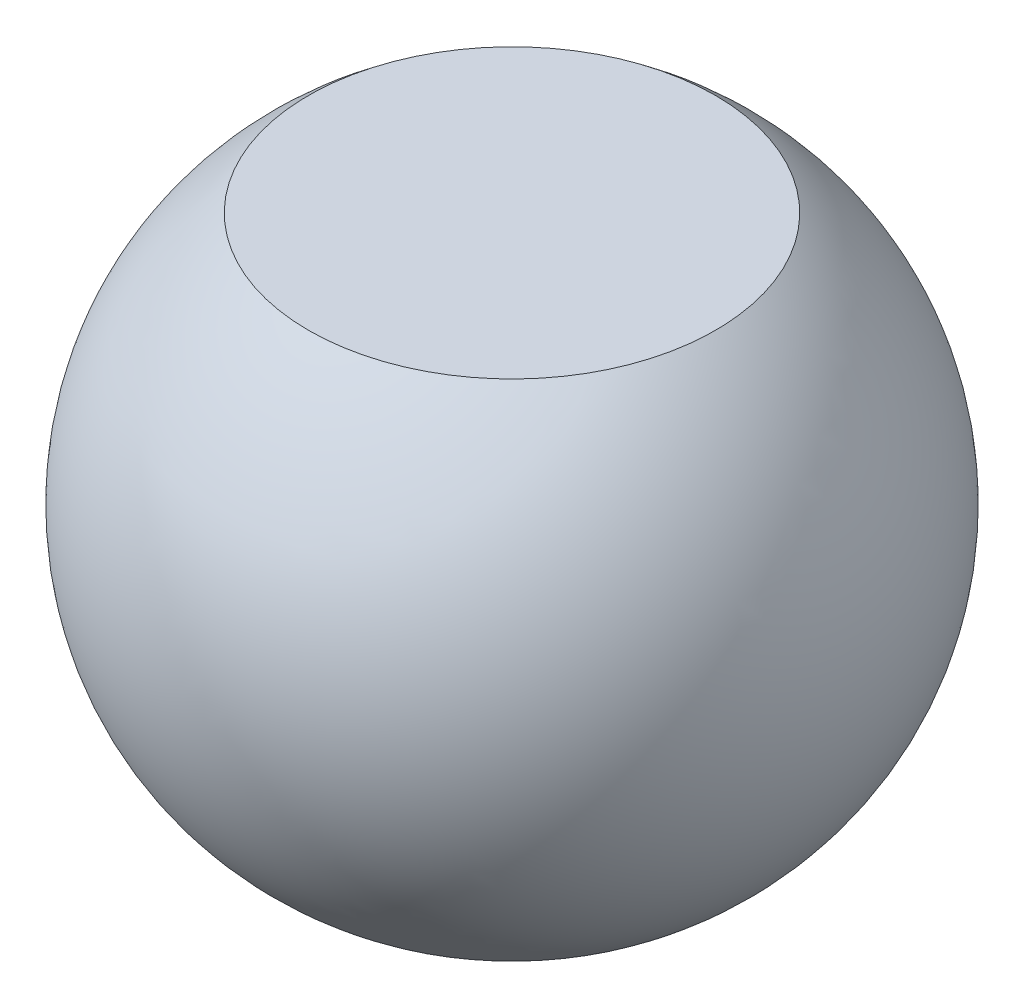
SolidWorks part; units mm, degrees
ref_plane "Front Plane" through (0, 0, 0) normal (0, 0, 1) x (1, 0, 0)
ref_plane "Top Plane" through (0, 0, 0) normal (0, 1, 0) x (1, 0, 0)
ref_plane "Right Plane" through (0, 0, 0) normal (1, 0, 0) x (0, 0, -1)
sketch "Sketch2" plane through (0, 0, 0) normal (1, 0, 0) x (0, 0, -1)
  line L0 (0, 0) -> (0, 805) construction
  line L1 (0, 0) -> (323, 0) construction
  line L2 (323, 0) -> (0, 0)
  line L3 (0, 805) -> (324.4168, 805)
  line L4 (0, 0) -> (0, 805)
  arc A0 (323, 0) -> (324.4168, 805) centre (23.7135, 403.028) ccw
  dimension "D3" = 502
  dimension "D1" = 323
  dimension "D2" = 805
revolve "Revolve1" add sketch "Sketch2" angle 360 about L4
sketch "Sketch3" plane through (0, 0, 0) normal (0, 0, 1) x (1, 0, 0)
  line L0 (-893, 784) -> (-745.515, 820.7721)
  line L1 (-893, 784) -> (-703.8317, 784) construction
  line L2 (-124.0567, 112.3589) -> (-741.9433, 112.3589) construction
  line L3 (-535.9692, 694.9822) -> (-1250.0308, 873.0178) construction
  arc A0 (-502.1573, 555) -> (-433, 112.3589) centre (-23.7135, 403.028) ccw
  arc A1 (-324.4168, 805) -> (-323, 0) centre (-23.7135, 403.028) ccw construction
  spline S0 degree 3 poles (-893, 784) (-661.7462, 726.3419) (-757, 112.3589) (-433, 112.3589) knots 0 0 0 0 1 1 1 1
  spline S1 degree 3 poles (-745.515, 820.7721) (-621.8172, 756.7965) (-634.4005, 616.5506) (-502.1573, 555) knots 0 0 0 0 1 1 1 1
  dimension "D7" = 972
  dimension "D8" = 14
  dimension "D9" = 715
  dimension "D1" = 433
  dimension "D2" = 555
  dimension "D3" = 152
  dimension "D4" = 14
  dimension "D5" = 784
  dimension "D6" = 893
